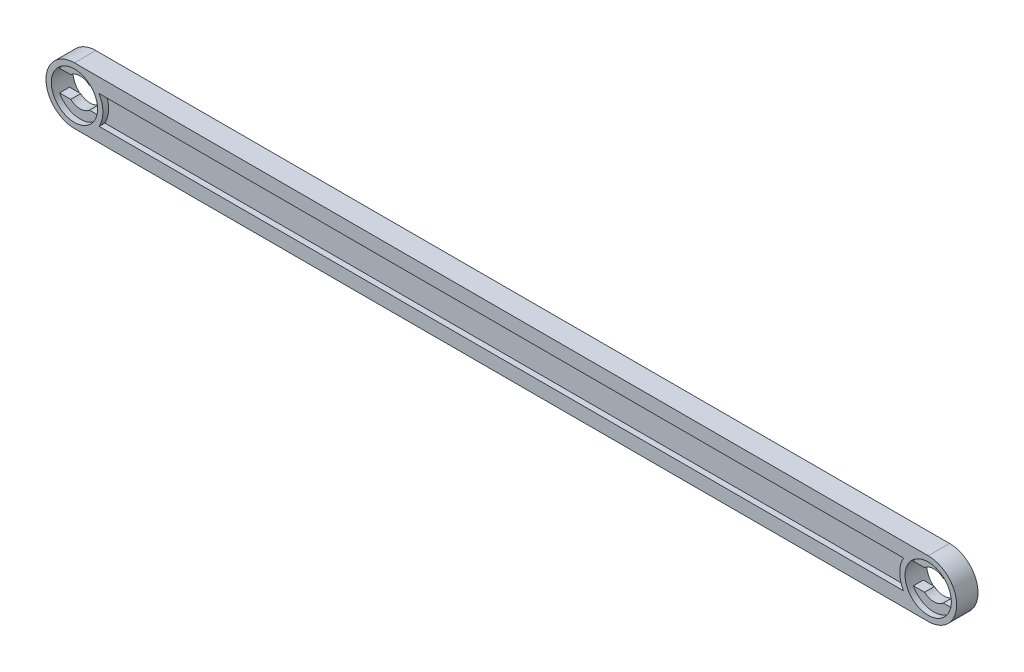
SolidWorks part; units mm, degrees
note: The reader was unsure of these and kept them because the rebuilt part matched: shared geometry of "草图3<2>".
ref_plane "前视基准面" through (0, 0, 0) normal (0, 0, 1) x (1, 0, 0)
ref_plane "上视基准面" through (0, 0, 0) normal (0, 1, 0) x (1, 0, 0)
ref_plane "右视基准面" through (0, 0, 0) normal (1, 0, 0) x (0, 0, -1)
sketch "草图1" plane through (0, 0, 0) normal (0, 0, 1) x (1, 0, 0)
  line L1 (0, 4) -> (120, 4)
  line L3 (0, -4) -> (120, -4)
  arc A0 (0, 4) -> (0, -4) centre (0, 0) ccw
  arc A1 (120, -4) -> (120, 4) centre (120, 0) ccw
extrude "凸台-拉伸1" add sketch "草图1" against normal blind 3
sketch "草图2" plane through (0, 0, 0) normal (0, 0, 1) x (1, 0, 0)
  line L0 (1.3229, -1.5) -> (2.8831, -1.5)
  line L1 (-2.8831, -1.5) -> (-1.3229, -1.5)
  line L2 (1.3229, 1.5) -> (2.8831, 1.5)
  line L3 (-2.8831, 1.5) -> (-1.3229, 1.5)
  arc A0 (1.3229, 1.5) -> (-1.3229, 1.5) centre (0, 0) ccw
  arc A1 (-2.8831, 1.5) -> (-2.8831, -1.5) centre (0, 0) ccw
  arc A3 (2.8831, -1.5) -> (2.8831, 1.5) centre (0, 0) ccw
  arc A4 (-1.3229, -1.5) -> (1.3229, -1.5) centre (0, 0) ccw
extrude "切除-拉伸1" cut sketch "草图2" against normal up to next
sketch "草图3" plane through (0, 0, 0) normal (0, 0, 1) x (1, 0, 0)
  circle A1 centre (0, 0) radius 3.25
extrude "切除-拉伸2" cut sketch "草图3" against normal blind 0.8
extrude "切除-拉伸3" cut sketch "草图3<2>" along normal blind 0.8 from offset 3 offset against normal yes
sketch "草图3<2>" plane through (0, 0, 0) normal (0, 0, 1) x (1, 0, 0) same geometry as "草图3"
ref_plane "基准面1" through (60, 0, 0) normal (1, 0, 0) x (0, 0, -1)
mirror "镜向1" about plane through (60, 0, 0) normal (1, 0, 0) of "切除-拉伸3", "切除-拉伸2", "切除-拉伸1"
sketch "草图4" plane through (0, 0, 0) normal (0, 0, 1) x (1, 0, 0)
  line L0 (3.4641, 2) -> (116.5359, 2)
  line L2 (3.4641, -2) -> (116.5359, -2)
  arc A0 (3.4641, -2) -> (3.4641, 2) centre (0, 0) ccw
  arc A2 (116.5359, 2) -> (116.5359, -2) centre (120, 0) ccw
extrude "切除-拉伸4" cut sketch "草图4" against normal blind 0.8
sketch "草图5" plane through (0, 0, -3) normal (0, 0, -1) x (-1, 0, 0)
  line L1 (-116, -2) -> (-4, -2)
  line L2 (-116, -2) -> (-116, 2)
  line L3 (-116, 2) -> (-4, 2)
  line L4 (-4, -2) -> (-4, 2)
extrude "切除-拉伸5" cut sketch "草图5" against normal blind 0.8
